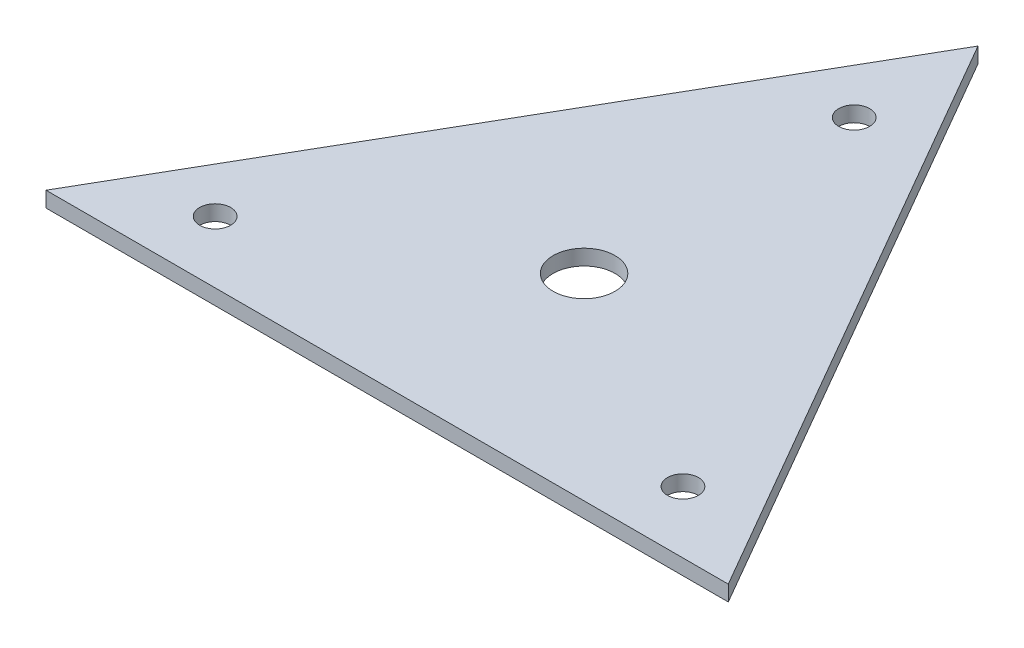
SolidWorks part; units mm, degrees
ref_plane "Front Plane" through (0, 0, 0) normal (0, 0, 1) x (1, 0, 0)
ref_plane "Top Plane" through (0, 0, 0) normal (0, 1, 0) x (1, 0, 0)
ref_plane "Right Plane" through (0, 0, 0) normal (1, 0, 0) x (0, 0, -1)
sketch "Sketch1" plane through (0, 0, 0) normal (0, 1, 0) x (1, 0, 0)
  line L0 (0, 0) -> (139.954, 0)
  line L1 (69.977, 121.2037) -> (139.954, 0)
  line L2 (69.977, 121.2037) -> (0, 0)
  line L3 (69.977, 40.4012) -> (69.977, 121.2037) construction
  line L4 (69.977, 40.4012) -> (0, 0) construction
  line L5 (69.977, 40.4012) -> (139.954, 0) construction
  circle A0 centre (69.977, 40.4012) radius 6.35
  circle A1 centre (117.957, 12.7) radius 3.175
  circle A2 centre (21.997, 12.7) radius 3.175
  circle A3 centre (69.977, 95.8037) radius 3.175
  dimension "D4" = 12.7
  dimension "D5" = 30
  dimension "D7" = 6.35
  dimension "D8" = 6.35
  dimension "D10" = 6.35
  dimension "D1" = 139.954
  dimension "D2" = 139.954
  dimension "D3" = 60
  dimension "D6" = 25.4
  dimension "D9" = 25.4
  dimension "D11" = 25.4
extrude "Boss-Extrude1" add sketch "Sketch1" along normal blind 3.175
sketch "Sketch2" plane through (0, 0, 0) normal (0, 1, 0) x (1, 0, 0)
  line L0 (117.957, 12.7) -> (21.997, 12.7) construction
  line L1 (21.997, 12.7) -> (69.977, 95.8037) construction
  line L2 (69.977, 95.8037) -> (117.957, 12.7) construction
  circle A0 centre (93.967, 54.2519) radius 6.35
  circle A1 centre (69.977, 12.7) radius 6.35
  circle A2 centre (45.987, 54.2519) radius 6.35
  dimension "D1" = 12.7
  dimension "D2" = 12.7
  dimension "D3" = 12.7
extrude "Cut-Extrude1" cut sketch "Sketch2" along normal blind 0.254
